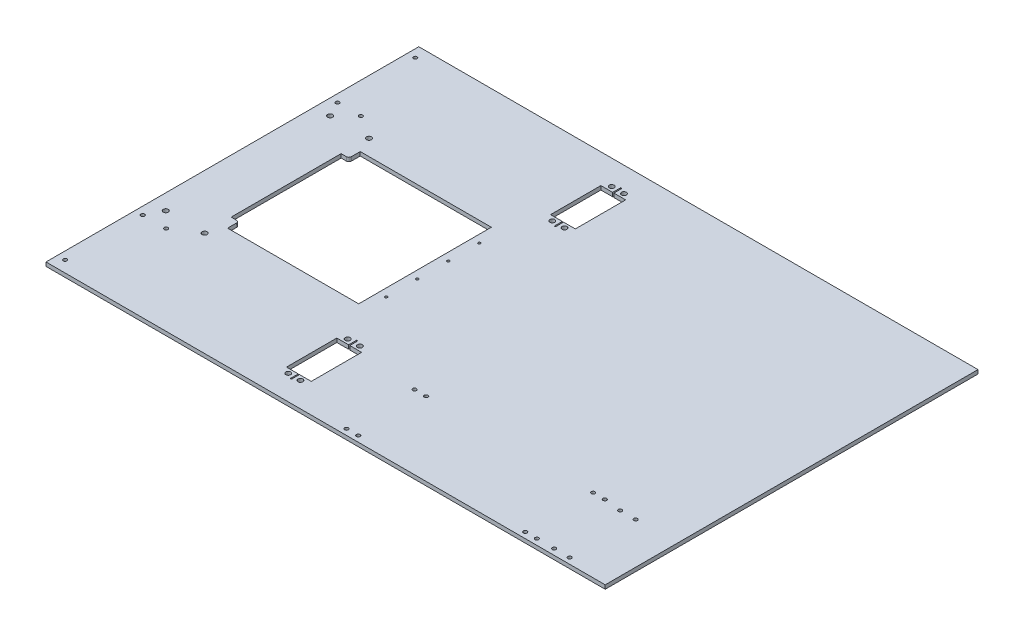
SolidWorks part; units mm, degrees
ref_plane "Front Plane" through (0, 0, 0) normal (0, 0, 1) x (1, 0, 0)
ref_plane "Top Plane" through (0, 0, 0) normal (0, 1, 0) x (1, 0, 0)
ref_plane "Right Plane" through (0, 0, 0) normal (1, 0, 0) x (0, 0, -1)
sketch "Sketch1" plane through (0, 0, 0) normal (0, 1, 0) x (1, 0, 0)
  line L1 (-228.6, -152.4) -> (228.6, -152.4)
  line L2 (-228.6, -152.4) -> (-228.6, 152.4)
  line L3 (-228.6, 152.4) -> (228.6, 152.4)
  line L4 (228.6, -152.4) -> (228.6, 152.4)
  line L5 (-228.6, -152.4) -> (228.6, 152.4) construction
  line L6 (-228.6, 152.4) -> (228.6, -152.4) construction
  point P0 (0, 0)
  dimension "D1" = 304.8
  dimension "D2" = 457.2
extrude "Boss-Extrude1" add sketch "Sketch1" along normal blind 3.175 contours L3 L4 L1 L2
sketch "Sketch2" plane through (0, 3.175, 0) normal (0, 1, 0) x (1, 0, 0)
  circle A0 centre (-184.15, -67.1976) radius 2.0635 construction
  circle A1 centre (-215.9, -67.1976) radius 2.0635 construction
  circle A2 centre (-184.15, 67.1976) radius 2.0635 construction
  circle A3 centre (-215.9, 67.1976) radius 2.0635 construction
  circle A6 centre (-184.15, -67.1976) radius 2.0635
  circle A7 centre (-215.9, -67.1976) radius 2.0635
  circle A8 centre (-184.15, 67.1976) radius 2.0635
  circle A9 centre (-215.9, 67.1976) radius 2.0635
extrude "Cut-Extrude1" cut sketch "Sketch2" against normal through all
sketch "Sketch3" plane through (0, 3.175, 0) normal (0, 1, 0) x (1, 0, 0)
  line L0 (-228.6, 0) -> (228.6, 0) construction
  line L1 (-228.6, -152.4) -> (-228.6, 152.4) construction
  line L2 (228.6, -152.4) -> (228.6, 152.4) construction
sketch "Sketch4" plane through (0, 3.175, 0) normal (0, 1, 0) x (1, 0, 0)
  line L0 (-184.658, 44.958) -> (-184.658, -44.958)
  line L1 (-184.658, -44.958) -> (-180.34, -44.958)
  line L2 (-178.308, -46.99) -> (-178.308, -54.229)
  line L3 (-178.308, -54.229) -> (-71.12, -54.229)
  line L4 (-71.12, -54.229) -> (-71.12, 54.229)
  line L5 (-71.12, 54.229) -> (-178.308, 54.229)
  line L6 (-178.308, 54.229) -> (-178.308, 46.99)
  line L7 (-180.34, 44.958) -> (-184.658, 44.958)
  line L8 (-184.15, 44.45) -> (-184.15, -44.45)
  line L9 (-180.34, 44.45) -> (-184.15, 44.45)
  line L10 (-177.8, 53.721) -> (-177.8, 46.99)
  line L11 (-71.628, 53.721) -> (-177.8, 53.721)
  line L12 (-71.628, -53.721) -> (-71.628, 53.721)
  line L13 (-177.8, -53.721) -> (-71.628, -53.721)
  line L14 (-177.8, -46.99) -> (-177.8, -53.721)
  line L15 (-184.15, -44.45) -> (-180.34, -44.45)
  line L16 (-184.15, 44.45) -> (-184.15, -44.45) construction
  line L17 (-180.34, 44.45) -> (-184.15, 44.45) construction
  line L18 (-177.8, 53.721) -> (-177.8, 46.99) construction
  line L19 (-71.628, 53.721) -> (-177.8, 53.721) construction
  line L20 (-71.628, -53.721) -> (-71.628, 53.721) construction
  line L21 (-177.8, -53.721) -> (-71.628, -53.721) construction
  line L22 (-177.8, -46.99) -> (-177.8, -53.721) construction
  line L23 (-184.15, -44.45) -> (-180.34, -44.45) construction
  arc A0 (-178.308, -46.99) -> (-180.34, -44.958) centre (-180.34, -46.99) ccw
  arc A1 (-180.34, 44.958) -> (-178.308, 46.99) centre (-180.34, 46.99) ccw
  arc A2 (-180.34, 44.45) -> (-177.8, 46.99) centre (-180.34, 46.99) ccw
  arc A3 (-177.8, -46.99) -> (-180.34, -44.45) centre (-180.34, -46.99) ccw
  arc A4 (-180.34, 44.45) -> (-177.8, 46.99) centre (-180.34, 46.99) ccw construction
  arc A5 (-177.8, -46.99) -> (-180.34, -44.45) centre (-180.34, -46.99) ccw construction
  dimension "D1" = 0
  dimension "D2" = 0.508
extrude "Cut-Extrude2" cut sketch "Sketch4" against normal up to next
sketch "Sketch5" plane through (0, 3.175, 0) normal (0, 1, 0) x (1, 0, 0)
  circle A0 centre (-203.2, 79.629) radius 1.5 construction
  circle A1 centre (-222.25, 143.129) radius 1.5 construction
  circle A2 centre (-222.25, 79.629) radius 1.5 construction
  circle A3 centre (-203.2, -79.629) radius 1.5 construction
  circle A4 centre (-222.25, -79.629) radius 1.5 construction
  circle A5 centre (-222.25, -143.129) radius 1.5 construction
  circle A6 centre (-203.2, 79.629) radius 1.5
  circle A7 centre (-222.25, 143.129) radius 1.5
  circle A8 centre (-222.25, 79.629) radius 1.5
  circle A9 centre (-203.2, -79.629) radius 1.5
  circle A10 centre (-222.25, -79.629) radius 1.5
  circle A11 centre (-222.25, -143.129) radius 1.5
extrude "Cut-Extrude3" cut sketch "Sketch5" against normal through all
sketch "Sketch7" plane through (0, 3.175, 0) normal (0, 1, 0) x (1, 0, 0)
  line L0 (-55.847, -87.373) -> (-35.593, -128.527) construction
  line L1 (-55.847, -87.373) -> (-46.22, -87.373)
  line L2 (-55.847, -87.373) -> (-55.847, -128.527)
  line L3 (-55.847, -128.527) -> (-46.22, -128.527)
  line L4 (-35.593, -87.373) -> (-35.593, -128.527)
  line L5 (-35.593, -87.373) -> (-55.847, -128.527) construction
  line L6 (-50.72, -83.65) -> (-40.72, -132.25) construction
  line L7 (-50.72, -132.25) -> (-40.72, -83.65) construction
  line L9 (-228.6, -152.4) -> (228.6, -152.4) construction
  line L10 (-45.22, -128.527) -> (-35.593, -128.527)
  line L12 (-46.22, -128.527) -> (-46.22, -135.131)
  line L13 (-46.22, -135.131) -> (-45.22, -135.131)
  line L14 (-45.22, -128.527) -> (-45.22, -135.131)
  line L15 (-45.72, -107.95) -> (-2.6371, -107.95) construction
  line L16 (-46.22, -80.769) -> (-45.22, -80.769)
  line L17 (-46.22, -87.373) -> (-46.22, -80.769)
  line L18 (-45.22, -87.373) -> (-45.22, -80.769)
  line L19 (-45.22, -87.373) -> (-35.593, -87.373)
  line L20 (-228.6, -152.4) -> (-228.6, 152.4) construction
  circle A0 centre (-50.72, -132.25) radius 2
  circle A1 centre (-40.72, -132.25) radius 2
  circle A2 centre (-50.72, -83.65) radius 2
  circle A3 centre (-40.72, -83.65) radius 2
  point P8 (-45.72, -135.131)
  point P17 (-45.72, -107.95)
  point P18 (-45.72, -107.95)
  dimension "D1" = 41.154
  dimension "D3" = 20.254
  dimension "D5" = 4
  dimension "D6" = 44.45
  dimension "D2" = 10
  dimension "D4" = 48.6
  dimension "D7" = 1
  dimension "D8" = 6.604
  dimension "D9" = 182.88
extrude "Cut-Extrude5" cut sketch "Sketch7" against normal through all
mirror "Mirror1" about plane through (0, 0, 0) normal (0, 0, 1) of "Cut-Extrude5"
sketch "Sketch8" plane through (0, 3.175, 0) normal (0, 1, 0) x (1, 0, 0)
  circle A1 centre (-64.77, -38.1) radius 1
  circle A2 centre (-64.77, -38.1) radius 1
  circle A3 centre (-64.77, -12.7) radius 1
  circle A4 centre (-64.77, -12.7) radius 1
  circle A5 centre (-64.77, 12.7) radius 1
  circle A6 centre (-64.77, 12.7) radius 1
  circle A7 centre (-64.77, 38.1) radius 1
  circle A8 centre (-64.77, 38.1) radius 1
  dimension "D1" = 0
  dimension "D2" = 0
  dimension "D3" = 0
  dimension "D4" = 0
extrude "Cut-Extrude6" cut sketch "Sketch8" against normal through all
sketch "Sketch12" plane through (0, 3.175, 0) normal (0, 1, 0) x (1, 0, 0)
  circle A0 centre (194.77, -93.6625) radius 1.5 construction
  circle A1 centre (182.07, -93.6625) radius 1.5 construction
  circle A2 centre (194.77, -147.6375) radius 1.5 construction
  circle A3 centre (182.07, -147.6375) radius 1.5 construction
  circle A4 centre (167.9575, -92.075) radius 1.5 construction
  circle A5 centre (158.4325, -92.075) radius 1.5 construction
  circle A6 centre (167.9575, -147.6375) radius 1.5 construction
  circle A7 centre (158.4325, -147.6375) radius 1.5 construction
  circle A8 centre (21.9075, -147.6375) radius 1.5 construction
  circle A9 centre (12.3825, -147.6375) radius 1.5 construction
  circle A10 centre (12.3825, -92.075) radius 1.5 construction
  circle A11 centre (21.9075, -92.075) radius 1.5 construction
  circle A12 centre (194.77, -93.6625) radius 1.5
  circle A13 centre (182.07, -93.6625) radius 1.5
  circle A14 centre (194.77, -147.6375) radius 1.5
  circle A15 centre (182.07, -147.6375) radius 1.5
  circle A16 centre (167.9575, -92.075) radius 1.5
  circle A17 centre (158.4325, -92.075) radius 1.5
  circle A18 centre (167.9575, -147.6375) radius 1.5
  circle A19 centre (158.4325, -147.6375) radius 1.5
  circle A20 centre (21.9075, -147.6375) radius 1.5
  circle A21 centre (12.3825, -147.6375) radius 1.5
  circle A22 centre (12.3825, -92.075) radius 1.5
  circle A23 centre (21.9075, -92.075) radius 1.5
extrude "Cut-Extrude7" cut sketch "Sketch12" against normal through all
equation "\"tightTol\"= 0.005in"
equation "\"normTol\"= 0.01in"
equation "\"looseTol\"= 0.02in"
equation "\"D2@Sketch4\"=\"looseTol\""
